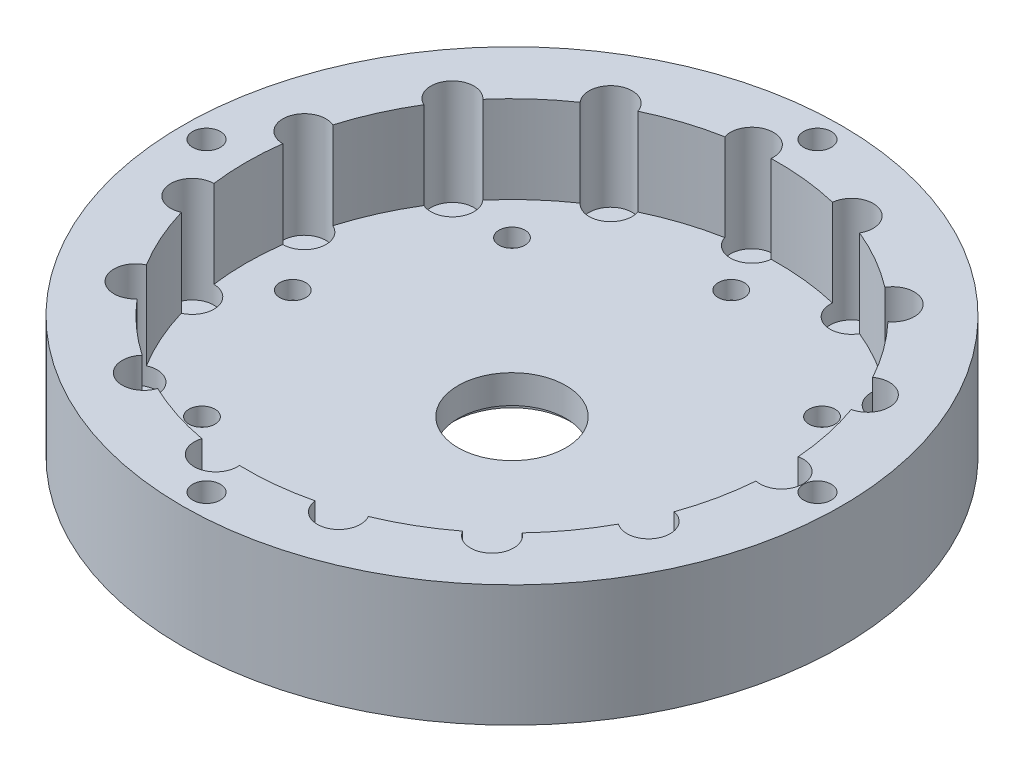
SolidWorks part; units mm, degrees
ref_plane "Front Plane" through (0, 0, 0) normal (0, 0, 1) x (1, 0, 0)
ref_plane "Top Plane" through (0, 0, 0) normal (0, 1, 0) x (1, 0, 0)
ref_plane "Right Plane" through (0, 0, 0) normal (1, 0, 0) x (0, 0, -1)
sketch "Sketch1" plane through (0, 0, 0) normal (0, 1, 0) x (1, 0, 0)
  line L0 (0, 0) -> (-42.5, 0) construction
  circle A0 centre (0, 0) radius 7.5
  circle A1 centre (0, 0) radius 45.85
  circle A2 centre (0, 0) radius 37.5 construction
  circle A3 centre (37.5, 0) radius 3
  circle A4 centre (34.258, 15.2526) radius 3
  circle A5 centre (25.0924, 27.8679) radius 3
  circle A6 centre (11.5881, 35.6646) radius 3
  circle A7 centre (-3.9198, 37.2946) radius 3
  circle A8 centre (-18.75, 32.476) radius 3
  circle A9 centre (-30.3381, 22.0419) radius 3
  circle A10 centre (-36.6805, 7.7967) radius 3
  circle A11 centre (-36.6805, -7.7967) radius 3
  circle A12 centre (-30.3381, -22.0419) radius 3
  circle A13 centre (-18.75, -32.476) radius 3
  circle A14 centre (-3.9198, -37.2946) radius 3
  circle A15 centre (11.5881, -35.6646) radius 3
  circle A16 centre (25.0924, -27.8679) radius 3
  circle A17 centre (34.258, -15.2526) radius 3
  circle A19 centre (0, 0) radius 30.5 construction
  circle A20 centre (30.5, 0) radius 1.8125
  circle A21 centre (21.5668, -21.5668) radius 1.8125
  circle A22 centre (0, -30.5) radius 1.8125
  circle A23 centre (-21.5668, -21.5668) radius 1.8125
  circle A24 centre (-30.5, 0) radius 1.8125
  circle A25 centre (-21.5668, 21.5668) radius 1.8125
  circle A26 centre (0, 30.5) radius 1.8125
  circle A27 centre (21.5668, 21.5668) radius 1.8125
  arc A28 (36.8833, 2.9359) -> (34.8888, 12.3197) centre (0, 0) ccw
  arc A29 (34.8888, -12.3197) -> (36.8833, -2.9359) centre (0, 0) ccw
  arc A30 (26.8616, -25.4451) -> (32.5004, -17.6839) centre (0, 0) ccw
  arc A31 (14.1898, -34.1709) -> (22.4979, -29.3742) centre (0, 0) ccw
  arc A32 (-0.9355, -36.9882) -> (8.6053, -35.9854) centre (0, 0) ccw
  arc A33 (-15.8991, -33.4099) -> (-6.7752, -36.3744) centre (0, 0) ccw
  arc A34 (-28.1135, -24.0547) -> (-20.9843, -30.4739) centre (0, 0) ccw
  arc A35 (-35.4669, -10.5403) -> (-31.5649, -19.3043) centre (0, 0) ccw
  arc A36 (-36.6878, 4.7967) -> (-36.6878, -4.7967) centre (0, 0) ccw
  arc A37 (-31.5649, 19.3043) -> (-35.4669, 10.5403) centre (0, 0) ccw
  arc A38 (-20.9843, 30.4739) -> (-28.1135, 24.0547) centre (0, 0) ccw
  arc A39 (-6.7752, 36.3744) -> (-15.8991, 33.4099) centre (0, 0) ccw
  arc A40 (8.6053, 35.9854) -> (-0.9355, 36.9882) centre (0, 0) ccw
  arc A41 (22.4979, 29.3742) -> (14.1898, 34.1709) centre (0, 0) ccw
  arc A42 (32.5004, 17.6839) -> (26.8616, 25.4451) centre (0, 0) ccw
  circle A43 centre (-42.5, 0) radius 1.5635
  circle A44 centre (0, 42.5) radius 1.5635
  circle A45 centre (42.5, 0) radius 1.5635
  circle A46 centre (0, 0) radius 8.25
  circle A47 centre (0, -42.5) radius 1.5635
  point P38 (0, 0)
  point P57 (0, 0)
  point P87 (0, 0)
  point P92 (0, 0)
  dimension "D2" = 15
  dimension "D3" = 75
  dimension "D4" = 91.7
  dimension "D5" = 6
  dimension "D8" = 3.625
  dimension "D9" = 61
  dimension "D6" = 37
  dimension "D12" = 3.127
  dimension "D14" = 16.5
  dimension "D11" = 42.5
  dimension "D1" = 15
  dimension "D7" = 8
  dimension "D10" = 15
  dimension "D13" = 4
extrude "Boss-Extrude1" add sketch "Sketch1" against normal blind 4.7625 contours A4 A42 A5 A41 A6 A40 A7 A39 A8 A38 A9 A37 A10 A36 A11 A35 A12 A34 A13 A33 A14 A32 A15 A31 A16 A30 A17 A29 A3 A28 A0 A20 A21 A22 A23 A24 A25 A26 A27 | A3 | A17 | A4 | A5 | A6 | A7 | A8 | A9 | A10 | A11 | A12 | A13 | A14 | A15 | A16 | A1 A42 A4 A28 A3 A29 A17 A30 A16 A31 A15 A32 A14 A33 A13 A34 A12 A35 A11 A36 A10 A37 A9 A38 A8 A39 A7 A40 A6 A41 A5 | A22 | A23 | A24 | A25 | A26 | A27 | A20 | A21 | A46 A0 region at (-44.5532, 0, 0) region at (37.5, 0, 0) region at (33.4543, 0, 0) region at (34.258, 0, -15.2526) region at (34.258, 0, 15.2526) region at (25.0924, 0, -27.8679) region at (25.0924, 0, 27.8679) region at (11.5881, 0, -35.6646) region at (11.5881, 0, 35.6646) region at (-3.9198, 0, -37.2946) region at (-3.9198, 0, 37.2946) region at (-18.75, 0, -32.476) region at (-18.75, 0, 32.476) region at (-30.3381, 0, -22.0419) region at (-30.3381, 0, 22.0419) region at (-36.6805, 0, -7.7967) region at (-36.6805, 0, 7.7967) region at (30.5, 0, 0) region at (21.5668, 0, 21.5668) region at (0, 0, 30.5) region at (-21.5668, 0, 21.5668) region at (-30.5, 0, 0) region at (-21.5668, 0, -21.5668) region at (0, 0, -30.5) region at (21.5668, 0, -21.5668) region at (-8.0167, 0, 0)
extrude "Cut-Extrude1" cut sketch "Sketch1<6>" against normal blind 2.5 contours A24 | A25 | A26 | A27 | A20 | A21 | A22 | A23 | A10 | A11 | A9 | A12 | A13 | A14 | A15 | A16 | A17 | A3 | A4 | A5 | A6 | A7 | A8 region at (37.5, 0, 0) region at (34.258, 0, -15.2526) region at (34.258, 0, 15.2526) region at (25.0924, 0, -27.8679) region at (25.0924, 0, 27.8679) region at (11.5881, 0, -35.6646) region at (11.5881, 0, 35.6646) region at (-3.9198, 0, -37.2946) region at (-3.9198, 0, 37.2946) region at (-18.75, 0, -32.476) region at (-18.75, 0, 32.476) region at (-30.3381, 0, -22.0419) region at (-30.3381, 0, 22.0419) region at (-36.6805, 0, -7.7967) region at (-36.6805, 0, 7.7967) region at (30.5, 0, 0) region at (21.5668, 0, 21.5668) region at (0, 0, 30.5) region at (-21.5668, 0, 21.5668) region at (-30.5, 0, 0) region at (-21.5668, 0, -21.5668) region at (0, 0, -30.5) region at (21.5668, 0, -21.5668)
sketch "Sketch1<6>" plane through (0, 0, 0) normal (0, 1, 0) x (1, 0, 0) same geometry as "Sketch1"
extrude "Boss-Extrude2" add sketch "Sketch1<7>" along normal blind 12.15 contours A1 A42 A4 A28 A3 A29 A17 A30 A16 A31 A15 A32 A14 A33 A13 A34 A12 A35 A11 A36 A10 A37 A9 A38 A8 A39 A7 A40 A6 A41 A5 region at (-44.5532, 0, 0)
sketch "Sketch1<7>" plane through (0, 0, 0) normal (0, 1, 0) x (1, 0, 0) same geometry as "Sketch1"
sketch "Sketch2" plane through (0, 12.15, 0) normal (0, 1, 0) x (1, 0, 0)
  circle A0 centre (-42.5, 0) radius 1.925
  circle A3 centre (0, 42.5) radius 1.925
  circle A4 centre (42.5, 0) radius 1.925
  circle A5 centre (0, -42.5) radius 1.925
  point P10 (0, 0)
  point P14 (0, 0)
  dimension "D2" = 3.85
  dimension "D1" = 4
extrude "Cut-Extrude2" cut sketch "Sketch2" against normal blind 4
extrude "Cut-Extrude3" cut sketch "Sketch1<8>" along normal blind 0.8 from offset 4.7625 contours A46 A0 region at (-8.0167, 0, 0) offset against normal yes
sketch "Sketch1<8>" plane through (0, 0, 0) normal (0, 1, 0) x (1, 0, 0) same geometry as "Sketch1"
equation "\"D2@Sketch1\"=\"smallBearOD\"+\"smallBearOTight\""
equation "\"D3@Sketch1\"=\"pinCircleDiam\""
equation "\"D5@Sketch1\"=\"pinDiam\""
equation "\"D8@Sketch1\"=\"ballBearDiam\"+0.125mm"
equation "\"D1@Cut-Extrude1\"=\"ballBearDiam\"-1mm"
equation "\"D1@Boss-Extrude2\"=\"ballBearDiam\"*0.75mm+2*\"sheetThickness\""
equation "\"largeBearOD\"= 21mm"
equation "\"largeBearID\" = 15mm"
equation "\"largeBearOTight\"= 0.34375mm'calibrate - hold onto gears"
equation "\"largeBearITight\"= 0mm'calibrate - hold onto eccentric nut"
equation "\"largeBearFlangeDiam\" = 22.5mm"
equation "\"largeBearFlangeWidth\" = 0.8mm"
equation "\"smallBearOD\"= 15mm"
equation "\"smallBearOTight\"= 0mm'calibrate - hold onto bottom of gearbox"
equation "\"smallBearOLoose\"= 0mm'calibrate - able to take off topHat"
equation "\"smallBearID\" = 10mm"
equation "\"smallBearITight\" = 0mm'hold onto "
equation "\"pinCircleDiam\"= 75mm"
equation "\"pinDiam\"= 6mm"
equation "\"sheetThickness\"= 0.1875in"
equation "\"ballBearDiam\"= 3.5mm"
equation "\"thrustBearingThickness\"= 5mm'measure this irl and change"
equation "\"thrustBearingID\"= 0mm'measure this irl and change"
equation "\"thrustBearingOD\"= 0mm'measure this irl and change"
equation "\"eccentricity\" = 1mm"
equation "\"D6@Sketch1\"=(\"pinCircleDiam\"-1)/2"
equation "\"D1@Boss-Extrude1\"=\"sheetThickness\""
equation "\"D19@Cut-Extrude3\"=\"sheetThickness\""
